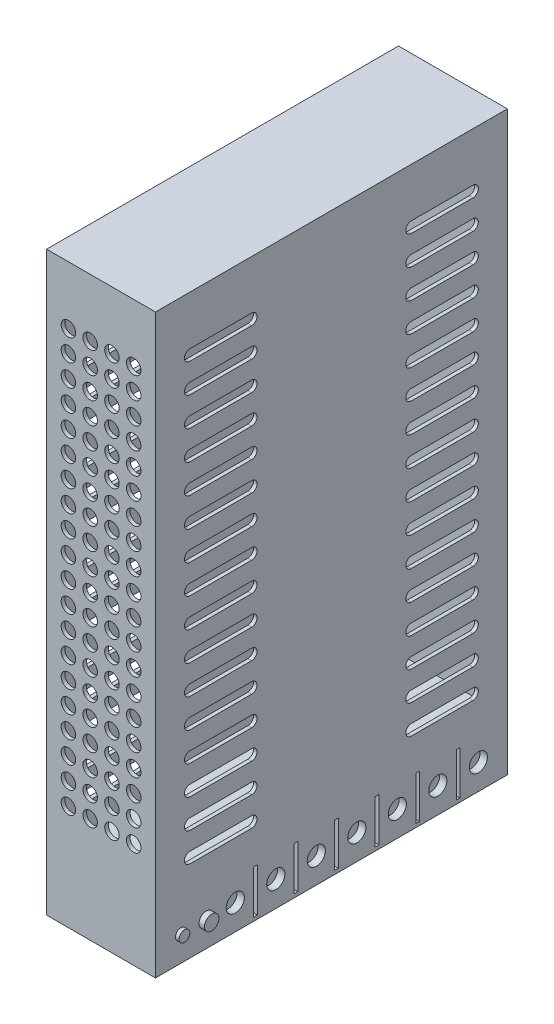
SolidWorks part; units mm, degrees
ref_plane "Front Plane" through (0, 0, 0) normal (0, 0, 1) x (1, 0, 0)
ref_plane "Top Plane" through (0, 0, 0) normal (0, 1, 0) x (1, 0, 0)
ref_plane "Right Plane" through (0, 0, 0) normal (1, 0, 0) x (0, 0, -1)
sketch "Sketch1" plane through (0, 0, 0) normal (0, 0, 1) x (1, 0, 0)
  line L1 (-15, 14) -> (15, 14)
  line L2 (-15, 14) -> (-15, 159)
  line L3 (-15, 159) -> (15, 159)
  line L4 (15, 14) -> (15, 159)
extrude "Case" add sketch "Sketch1" along normal blind 97
shell "Case_shell" thickness 1
sketch "Sketch2" plane through (0, 0, 0) normal (0, 0, 1) x (1, 0, 0)
  line L1 (-15, 0) -> (15, 0)
  line L2 (-15, 0) -> (-15, 14)
  line L3 (-15, 14) -> (15, 14)
  line L4 (15, 0) -> (15, 14)
extrude "Terminal_block" add sketch "Sketch2" along normal blind 97
ref_plane "Plane_x15" through (15, 0, 0) normal (1, 0, 0) x (0, 0, -1)
sketch "Sketch3" plane through (15, 0, 0) normal (1, 0, 0) x (0, 0, -1)
  circle A0 centre (-83, 7) radius 2
extrude "Pot" add sketch "Sketch3" along normal blind 1.5
sketch "Sketch4" plane through (15, 0, 0) normal (1, 0, 0) x (0, 0, -1)
  circle A0 centre (-90, 7) radius 1.5
extrude "LED" add sketch "Sketch4" along normal blind 1
ref_plane "Plane_z97" through (0, 0, 97) normal (0, 0, 1) x (1, 0, 0)
sketch "Sketch5" plane through (0, 0, 97) normal (0, 0, 1) x (1, 0, 0)
  circle A0 centre (-9, 29) radius 2
  circle A1 centre (-9, 35) radius 2
  circle A2 centre (-9, 41) radius 2
  circle A3 centre (-9, 47) radius 2
  circle A4 centre (-9, 53) radius 2
  circle A5 centre (-9, 59) radius 2
  circle A6 centre (-9, 65) radius 2
  circle A7 centre (-9, 71) radius 2
  circle A8 centre (-9, 77) radius 2
  circle A9 centre (-9, 83) radius 2
  circle A10 centre (-9, 89) radius 2
  circle A11 centre (-9, 95) radius 2
  circle A12 centre (-9, 101) radius 2
  circle A13 centre (-9, 107) radius 2
  circle A14 centre (-9, 113) radius 2
  circle A15 centre (-9, 119) radius 2
  circle A16 centre (-9, 125) radius 2
  circle A17 centre (-9, 131) radius 2
  circle A18 centre (-9, 137) radius 2
  circle A19 centre (-9, 143) radius 2
  circle A20 centre (-3, 29) radius 2
  circle A21 centre (-3, 35) radius 2
  circle A22 centre (-3, 41) radius 2
  circle A23 centre (-3, 47) radius 2
  circle A24 centre (-3, 53) radius 2
  circle A25 centre (-3, 59) radius 2
  circle A26 centre (-3, 65) radius 2
  circle A27 centre (-3, 71) radius 2
  circle A28 centre (-3, 77) radius 2
  circle A29 centre (-3, 83) radius 2
  circle A30 centre (-3, 89) radius 2
  circle A31 centre (-3, 95) radius 2
  circle A32 centre (-3, 101) radius 2
  circle A33 centre (-3, 107) radius 2
  circle A34 centre (-3, 113) radius 2
  circle A35 centre (-3, 119) radius 2
  circle A36 centre (-3, 125) radius 2
  circle A37 centre (-3, 131) radius 2
  circle A38 centre (-3, 137) radius 2
  circle A39 centre (-3, 143) radius 2
  circle A40 centre (3, 29) radius 2
  circle A41 centre (3, 35) radius 2
  circle A42 centre (3, 41) radius 2
  circle A43 centre (3, 47) radius 2
  circle A44 centre (3, 53) radius 2
  circle A45 centre (3, 59) radius 2
  circle A46 centre (3, 65) radius 2
  circle A47 centre (3, 71) radius 2
  circle A48 centre (3, 77) radius 2
  circle A49 centre (3, 83) radius 2
  circle A50 centre (3, 89) radius 2
  circle A51 centre (3, 95) radius 2
  circle A52 centre (3, 101) radius 2
  circle A53 centre (3, 107) radius 2
  circle A54 centre (3, 113) radius 2
  circle A55 centre (3, 119) radius 2
  circle A56 centre (3, 125) radius 2
  circle A57 centre (3, 131) radius 2
  circle A58 centre (3, 137) radius 2
  circle A59 centre (3, 143) radius 2
  circle A60 centre (9, 29) radius 2
  circle A61 centre (9, 35) radius 2
  circle A62 centre (9, 41) radius 2
  circle A63 centre (9, 47) radius 2
  circle A64 centre (9, 53) radius 2
  circle A65 centre (9, 59) radius 2
  circle A66 centre (9, 65) radius 2
  circle A67 centre (9, 71) radius 2
  circle A68 centre (9, 77) radius 2
  circle A69 centre (9, 83) radius 2
  circle A70 centre (9, 89) radius 2
  circle A71 centre (9, 95) radius 2
  circle A72 centre (9, 101) radius 2
  circle A73 centre (9, 107) radius 2
  circle A74 centre (9, 113) radius 2
  circle A75 centre (9, 119) radius 2
  circle A76 centre (9, 125) radius 2
  circle A77 centre (9, 131) radius 2
  circle A78 centre (9, 137) radius 2
  circle A79 centre (9, 143) radius 2
extrude "Perforation" cut sketch "Sketch5" against normal blind 1
sketch "Sketch6" plane through (15, 0, 0) normal (1, 0, 0) x (0, 0, -1)
  line L0 (-9.5, 24) -> (-26.5, 24) construction
  line L1 (-9.5, 22.5) -> (-26.5, 22.5)
  line L2 (-9.5, 25.5) -> (-26.5, 25.5)
  line L3 (-70.5, 24) -> (-87.5, 24) construction
  line L4 (-70.5, 22.5) -> (-87.5, 22.5)
  line L5 (-70.5, 25.5) -> (-87.5, 25.5)
  line L6 (-9.5, 32) -> (-26.5, 32) construction
  line L7 (-9.5, 30.5) -> (-26.5, 30.5)
  line L8 (-9.5, 33.5) -> (-26.5, 33.5)
  line L9 (-70.5, 32) -> (-87.5, 32) construction
  line L10 (-70.5, 30.5) -> (-87.5, 30.5)
  line L11 (-70.5, 33.5) -> (-87.5, 33.5)
  line L12 (-9.5, 40) -> (-26.5, 40) construction
  line L13 (-9.5, 38.5) -> (-26.5, 38.5)
  line L14 (-9.5, 41.5) -> (-26.5, 41.5)
  line L15 (-70.5, 40) -> (-87.5, 40) construction
  line L16 (-70.5, 38.5) -> (-87.5, 38.5)
  line L17 (-70.5, 41.5) -> (-87.5, 41.5)
  line L18 (-9.5, 48) -> (-26.5, 48) construction
  line L19 (-9.5, 46.5) -> (-26.5, 46.5)
  line L20 (-9.5, 49.5) -> (-26.5, 49.5)
  line L21 (-70.5, 48) -> (-87.5, 48) construction
  line L22 (-70.5, 46.5) -> (-87.5, 46.5)
  line L23 (-70.5, 49.5) -> (-87.5, 49.5)
  line L24 (-9.5, 56) -> (-26.5, 56) construction
  line L25 (-9.5, 54.5) -> (-26.5, 54.5)
  line L26 (-9.5, 57.5) -> (-26.5, 57.5)
  line L27 (-70.5, 56) -> (-87.5, 56) construction
  line L28 (-70.5, 54.5) -> (-87.5, 54.5)
  line L29 (-70.5, 57.5) -> (-87.5, 57.5)
  line L30 (-9.5, 64) -> (-26.5, 64) construction
  line L31 (-9.5, 62.5) -> (-26.5, 62.5)
  line L32 (-9.5, 65.5) -> (-26.5, 65.5)
  line L33 (-70.5, 64) -> (-87.5, 64) construction
  line L34 (-70.5, 62.5) -> (-87.5, 62.5)
  line L35 (-70.5, 65.5) -> (-87.5, 65.5)
  line L36 (-9.5, 72) -> (-26.5, 72) construction
  line L37 (-9.5, 70.5) -> (-26.5, 70.5)
  line L38 (-9.5, 73.5) -> (-26.5, 73.5)
  line L39 (-70.5, 72) -> (-87.5, 72) construction
  line L40 (-70.5, 70.5) -> (-87.5, 70.5)
  line L41 (-70.5, 73.5) -> (-87.5, 73.5)
  line L42 (-9.5, 80) -> (-26.5, 80) construction
  line L43 (-9.5, 78.5) -> (-26.5, 78.5)
  line L44 (-9.5, 81.5) -> (-26.5, 81.5)
  line L45 (-70.5, 80) -> (-87.5, 80) construction
  line L46 (-70.5, 78.5) -> (-87.5, 78.5)
  line L47 (-70.5, 81.5) -> (-87.5, 81.5)
  line L48 (-9.5, 88) -> (-26.5, 88) construction
  line L49 (-9.5, 86.5) -> (-26.5, 86.5)
  line L50 (-9.5, 89.5) -> (-26.5, 89.5)
  line L51 (-70.5, 88) -> (-87.5, 88) construction
  line L52 (-70.5, 86.5) -> (-87.5, 86.5)
  line L53 (-70.5, 89.5) -> (-87.5, 89.5)
  line L54 (-9.5, 96) -> (-26.5, 96) construction
  line L55 (-9.5, 94.5) -> (-26.5, 94.5)
  line L56 (-9.5, 97.5) -> (-26.5, 97.5)
  line L57 (-70.5, 96) -> (-87.5, 96) construction
  line L58 (-70.5, 94.5) -> (-87.5, 94.5)
  line L59 (-70.5, 97.5) -> (-87.5, 97.5)
  line L60 (-9.5, 104) -> (-26.5, 104) construction
  line L61 (-9.5, 102.5) -> (-26.5, 102.5)
  line L62 (-9.5, 105.5) -> (-26.5, 105.5)
  line L63 (-70.5, 104) -> (-87.5, 104) construction
  line L64 (-70.5, 102.5) -> (-87.5, 102.5)
  line L65 (-70.5, 105.5) -> (-87.5, 105.5)
  line L66 (-9.5, 112) -> (-26.5, 112) construction
  line L67 (-9.5, 110.5) -> (-26.5, 110.5)
  line L68 (-9.5, 113.5) -> (-26.5, 113.5)
  line L69 (-70.5, 112) -> (-87.5, 112) construction
  line L70 (-70.5, 110.5) -> (-87.5, 110.5)
  line L71 (-70.5, 113.5) -> (-87.5, 113.5)
  line L72 (-9.5, 120) -> (-26.5, 120) construction
  line L73 (-9.5, 118.5) -> (-26.5, 118.5)
  line L74 (-9.5, 121.5) -> (-26.5, 121.5)
  line L75 (-70.5, 120) -> (-87.5, 120) construction
  line L76 (-70.5, 118.5) -> (-87.5, 118.5)
  line L77 (-70.5, 121.5) -> (-87.5, 121.5)
  line L78 (-9.5, 128) -> (-26.5, 128) construction
  line L79 (-9.5, 126.5) -> (-26.5, 126.5)
  line L80 (-9.5, 129.5) -> (-26.5, 129.5)
  line L81 (-70.5, 128) -> (-87.5, 128) construction
  line L82 (-70.5, 126.5) -> (-87.5, 126.5)
  line L83 (-70.5, 129.5) -> (-87.5, 129.5)
  line L84 (-9.5, 136) -> (-26.5, 136) construction
  line L85 (-9.5, 134.5) -> (-26.5, 134.5)
  line L86 (-9.5, 137.5) -> (-26.5, 137.5)
  line L87 (-70.5, 136) -> (-87.5, 136) construction
  line L88 (-70.5, 134.5) -> (-87.5, 134.5)
  line L89 (-70.5, 137.5) -> (-87.5, 137.5)
  line L90 (-9.5, 144) -> (-26.5, 144) construction
  line L91 (-9.5, 142.5) -> (-26.5, 142.5)
  line L92 (-9.5, 145.5) -> (-26.5, 145.5)
  line L93 (-70.5, 144) -> (-87.5, 144) construction
  line L94 (-70.5, 142.5) -> (-87.5, 142.5)
  line L95 (-70.5, 145.5) -> (-87.5, 145.5)
  arc A0 (-9.5, 22.5) -> (-9.5, 25.5) centre (-9.5, 24) ccw
  arc A1 (-26.5, 25.5) -> (-26.5, 22.5) centre (-26.5, 24) ccw
  arc A2 (-70.5, 22.5) -> (-70.5, 25.5) centre (-70.5, 24) ccw
  arc A3 (-87.5, 25.5) -> (-87.5, 22.5) centre (-87.5, 24) ccw
  arc A4 (-9.5, 30.5) -> (-9.5, 33.5) centre (-9.5, 32) ccw
  arc A5 (-26.5, 33.5) -> (-26.5, 30.5) centre (-26.5, 32) ccw
  arc A6 (-70.5, 30.5) -> (-70.5, 33.5) centre (-70.5, 32) ccw
  arc A7 (-87.5, 33.5) -> (-87.5, 30.5) centre (-87.5, 32) ccw
  arc A8 (-9.5, 38.5) -> (-9.5, 41.5) centre (-9.5, 40) ccw
  arc A9 (-26.5, 41.5) -> (-26.5, 38.5) centre (-26.5, 40) ccw
  arc A10 (-70.5, 38.5) -> (-70.5, 41.5) centre (-70.5, 40) ccw
  arc A11 (-87.5, 41.5) -> (-87.5, 38.5) centre (-87.5, 40) ccw
  arc A12 (-9.5, 46.5) -> (-9.5, 49.5) centre (-9.5, 48) ccw
  arc A13 (-26.5, 49.5) -> (-26.5, 46.5) centre (-26.5, 48) ccw
  arc A14 (-70.5, 46.5) -> (-70.5, 49.5) centre (-70.5, 48) ccw
  arc A15 (-87.5, 49.5) -> (-87.5, 46.5) centre (-87.5, 48) ccw
  arc A16 (-9.5, 54.5) -> (-9.5, 57.5) centre (-9.5, 56) ccw
  arc A17 (-26.5, 57.5) -> (-26.5, 54.5) centre (-26.5, 56) ccw
  arc A18 (-70.5, 54.5) -> (-70.5, 57.5) centre (-70.5, 56) ccw
  arc A19 (-87.5, 57.5) -> (-87.5, 54.5) centre (-87.5, 56) ccw
  arc A20 (-9.5, 62.5) -> (-9.5, 65.5) centre (-9.5, 64) ccw
  arc A21 (-26.5, 65.5) -> (-26.5, 62.5) centre (-26.5, 64) ccw
  arc A22 (-70.5, 62.5) -> (-70.5, 65.5) centre (-70.5, 64) ccw
  arc A23 (-87.5, 65.5) -> (-87.5, 62.5) centre (-87.5, 64) ccw
  arc A24 (-9.5, 70.5) -> (-9.5, 73.5) centre (-9.5, 72) ccw
  arc A25 (-26.5, 73.5) -> (-26.5, 70.5) centre (-26.5, 72) ccw
  arc A26 (-70.5, 70.5) -> (-70.5, 73.5) centre (-70.5, 72) ccw
  arc A27 (-87.5, 73.5) -> (-87.5, 70.5) centre (-87.5, 72) ccw
  arc A28 (-9.5, 78.5) -> (-9.5, 81.5) centre (-9.5, 80) ccw
  arc A29 (-26.5, 81.5) -> (-26.5, 78.5) centre (-26.5, 80) ccw
  arc A30 (-70.5, 78.5) -> (-70.5, 81.5) centre (-70.5, 80) ccw
  arc A31 (-87.5, 81.5) -> (-87.5, 78.5) centre (-87.5, 80) ccw
  arc A32 (-9.5, 86.5) -> (-9.5, 89.5) centre (-9.5, 88) ccw
  arc A33 (-26.5, 89.5) -> (-26.5, 86.5) centre (-26.5, 88) ccw
  arc A34 (-70.5, 86.5) -> (-70.5, 89.5) centre (-70.5, 88) ccw
  arc A35 (-87.5, 89.5) -> (-87.5, 86.5) centre (-87.5, 88) ccw
  arc A36 (-9.5, 94.5) -> (-9.5, 97.5) centre (-9.5, 96) ccw
  arc A37 (-26.5, 97.5) -> (-26.5, 94.5) centre (-26.5, 96) ccw
  arc A38 (-70.5, 94.5) -> (-70.5, 97.5) centre (-70.5, 96) ccw
  arc A39 (-87.5, 97.5) -> (-87.5, 94.5) centre (-87.5, 96) ccw
  arc A40 (-9.5, 102.5) -> (-9.5, 105.5) centre (-9.5, 104) ccw
  arc A41 (-26.5, 105.5) -> (-26.5, 102.5) centre (-26.5, 104) ccw
  arc A42 (-70.5, 102.5) -> (-70.5, 105.5) centre (-70.5, 104) ccw
  arc A43 (-87.5, 105.5) -> (-87.5, 102.5) centre (-87.5, 104) ccw
  arc A44 (-9.5, 110.5) -> (-9.5, 113.5) centre (-9.5, 112) ccw
  arc A45 (-26.5, 113.5) -> (-26.5, 110.5) centre (-26.5, 112) ccw
  arc A46 (-70.5, 110.5) -> (-70.5, 113.5) centre (-70.5, 112) ccw
  arc A47 (-87.5, 113.5) -> (-87.5, 110.5) centre (-87.5, 112) ccw
  arc A48 (-9.5, 118.5) -> (-9.5, 121.5) centre (-9.5, 120) ccw
  arc A49 (-26.5, 121.5) -> (-26.5, 118.5) centre (-26.5, 120) ccw
  arc A50 (-70.5, 118.5) -> (-70.5, 121.5) centre (-70.5, 120) ccw
  arc A51 (-87.5, 121.5) -> (-87.5, 118.5) centre (-87.5, 120) ccw
  arc A52 (-9.5, 126.5) -> (-9.5, 129.5) centre (-9.5, 128) ccw
  arc A53 (-26.5, 129.5) -> (-26.5, 126.5) centre (-26.5, 128) ccw
  arc A54 (-70.5, 126.5) -> (-70.5, 129.5) centre (-70.5, 128) ccw
  arc A55 (-87.5, 129.5) -> (-87.5, 126.5) centre (-87.5, 128) ccw
  arc A56 (-9.5, 134.5) -> (-9.5, 137.5) centre (-9.5, 136) ccw
  arc A57 (-26.5, 137.5) -> (-26.5, 134.5) centre (-26.5, 136) ccw
  arc A58 (-70.5, 134.5) -> (-70.5, 137.5) centre (-70.5, 136) ccw
  arc A59 (-87.5, 137.5) -> (-87.5, 134.5) centre (-87.5, 136) ccw
  arc A60 (-9.5, 142.5) -> (-9.5, 145.5) centre (-9.5, 144) ccw
  arc A61 (-26.5, 145.5) -> (-26.5, 142.5) centre (-26.5, 144) ccw
  arc A62 (-70.5, 142.5) -> (-70.5, 145.5) centre (-70.5, 144) ccw
  arc A63 (-87.5, 145.5) -> (-87.5, 142.5) centre (-87.5, 144) ccw
  point P2 (-18, 24)
  point P7 (-79, 24)
  point P14 (-18, 32)
  point P21 (-79, 32)
  point P28 (-18, 40)
  point P35 (-79, 40)
  point P42 (-18, 48)
  point P49 (-79, 48)
  point P56 (-18, 56)
  point P63 (-79, 56)
  point P70 (-18, 64)
  point P77 (-79, 64)
  point P84 (-18, 72)
  point P91 (-79, 72)
  point P98 (-18, 80)
  point P105 (-79, 80)
  point P112 (-18, 88)
  point P119 (-79, 88)
  point P126 (-18, 96)
  point P133 (-79, 96)
  point P140 (-18, 104)
  point P147 (-79, 104)
  point P154 (-18, 112)
  point P161 (-79, 112)
  point P168 (-18, 120)
  point P175 (-79, 120)
  point P182 (-18, 128)
  point P189 (-79, 128)
  point P196 (-18, 136)
  point P203 (-79, 136)
  point P210 (-18, 144)
  point P217 (-79, 144)
  point P224 (0, 0)
extrude "Vents_R" cut sketch "Sketch6" against normal blind 1
ref_plane "Plane_xm15" through (-15, 0, 0) normal (1, 0, 0) x (0, 0, -1)
sketch "Sketch7" plane through (-15, 0, 0) normal (1, 0, 0) x (0, 0, -1)
  line L0 (-9.5, 24) -> (-26.5, 24) construction
  line L1 (-9.5, 22.5) -> (-26.5, 22.5)
  line L2 (-9.5, 25.5) -> (-26.5, 25.5)
  line L3 (-70.5, 24) -> (-87.5, 24) construction
  line L4 (-70.5, 22.5) -> (-87.5, 22.5)
  line L5 (-70.5, 25.5) -> (-87.5, 25.5)
  line L6 (-9.5, 32) -> (-26.5, 32) construction
  line L7 (-9.5, 30.5) -> (-26.5, 30.5)
  line L8 (-9.5, 33.5) -> (-26.5, 33.5)
  line L9 (-70.5, 32) -> (-87.5, 32) construction
  line L10 (-70.5, 30.5) -> (-87.5, 30.5)
  line L11 (-70.5, 33.5) -> (-87.5, 33.5)
  line L12 (-9.5, 40) -> (-26.5, 40) construction
  line L13 (-9.5, 38.5) -> (-26.5, 38.5)
  line L14 (-9.5, 41.5) -> (-26.5, 41.5)
  line L15 (-70.5, 40) -> (-87.5, 40) construction
  line L16 (-70.5, 38.5) -> (-87.5, 38.5)
  line L17 (-70.5, 41.5) -> (-87.5, 41.5)
  line L18 (-9.5, 48) -> (-26.5, 48) construction
  line L19 (-9.5, 46.5) -> (-26.5, 46.5)
  line L20 (-9.5, 49.5) -> (-26.5, 49.5)
  line L21 (-70.5, 48) -> (-87.5, 48) construction
  line L22 (-70.5, 46.5) -> (-87.5, 46.5)
  line L23 (-70.5, 49.5) -> (-87.5, 49.5)
  line L24 (-9.5, 56) -> (-26.5, 56) construction
  line L25 (-9.5, 54.5) -> (-26.5, 54.5)
  line L26 (-9.5, 57.5) -> (-26.5, 57.5)
  line L27 (-70.5, 56) -> (-87.5, 56) construction
  line L28 (-70.5, 54.5) -> (-87.5, 54.5)
  line L29 (-70.5, 57.5) -> (-87.5, 57.5)
  line L30 (-9.5, 64) -> (-26.5, 64) construction
  line L31 (-9.5, 62.5) -> (-26.5, 62.5)
  line L32 (-9.5, 65.5) -> (-26.5, 65.5)
  line L33 (-70.5, 64) -> (-87.5, 64) construction
  line L34 (-70.5, 62.5) -> (-87.5, 62.5)
  line L35 (-70.5, 65.5) -> (-87.5, 65.5)
  line L36 (-9.5, 72) -> (-26.5, 72) construction
  line L37 (-9.5, 70.5) -> (-26.5, 70.5)
  line L38 (-9.5, 73.5) -> (-26.5, 73.5)
  line L39 (-70.5, 72) -> (-87.5, 72) construction
  line L40 (-70.5, 70.5) -> (-87.5, 70.5)
  line L41 (-70.5, 73.5) -> (-87.5, 73.5)
  line L42 (-9.5, 80) -> (-26.5, 80) construction
  line L43 (-9.5, 78.5) -> (-26.5, 78.5)
  line L44 (-9.5, 81.5) -> (-26.5, 81.5)
  line L45 (-70.5, 80) -> (-87.5, 80) construction
  line L46 (-70.5, 78.5) -> (-87.5, 78.5)
  line L47 (-70.5, 81.5) -> (-87.5, 81.5)
  line L48 (-9.5, 88) -> (-26.5, 88) construction
  line L49 (-9.5, 86.5) -> (-26.5, 86.5)
  line L50 (-9.5, 89.5) -> (-26.5, 89.5)
  line L51 (-70.5, 88) -> (-87.5, 88) construction
  line L52 (-70.5, 86.5) -> (-87.5, 86.5)
  line L53 (-70.5, 89.5) -> (-87.5, 89.5)
  line L54 (-9.5, 96) -> (-26.5, 96) construction
  line L55 (-9.5, 94.5) -> (-26.5, 94.5)
  line L56 (-9.5, 97.5) -> (-26.5, 97.5)
  line L57 (-70.5, 96) -> (-87.5, 96) construction
  line L58 (-70.5, 94.5) -> (-87.5, 94.5)
  line L59 (-70.5, 97.5) -> (-87.5, 97.5)
  line L60 (-9.5, 104) -> (-26.5, 104) construction
  line L61 (-9.5, 102.5) -> (-26.5, 102.5)
  line L62 (-9.5, 105.5) -> (-26.5, 105.5)
  line L63 (-70.5, 104) -> (-87.5, 104) construction
  line L64 (-70.5, 102.5) -> (-87.5, 102.5)
  line L65 (-70.5, 105.5) -> (-87.5, 105.5)
  line L66 (-9.5, 112) -> (-26.5, 112) construction
  line L67 (-9.5, 110.5) -> (-26.5, 110.5)
  line L68 (-9.5, 113.5) -> (-26.5, 113.5)
  line L69 (-70.5, 112) -> (-87.5, 112) construction
  line L70 (-70.5, 110.5) -> (-87.5, 110.5)
  line L71 (-70.5, 113.5) -> (-87.5, 113.5)
  line L72 (-9.5, 120) -> (-26.5, 120) construction
  line L73 (-9.5, 118.5) -> (-26.5, 118.5)
  line L74 (-9.5, 121.5) -> (-26.5, 121.5)
  line L75 (-70.5, 120) -> (-87.5, 120) construction
  line L76 (-70.5, 118.5) -> (-87.5, 118.5)
  line L77 (-70.5, 121.5) -> (-87.5, 121.5)
  line L78 (-9.5, 128) -> (-26.5, 128) construction
  line L79 (-9.5, 126.5) -> (-26.5, 126.5)
  line L80 (-9.5, 129.5) -> (-26.5, 129.5)
  line L81 (-70.5, 128) -> (-87.5, 128) construction
  line L82 (-70.5, 126.5) -> (-87.5, 126.5)
  line L83 (-70.5, 129.5) -> (-87.5, 129.5)
  line L84 (-9.5, 136) -> (-26.5, 136) construction
  line L85 (-9.5, 134.5) -> (-26.5, 134.5)
  line L86 (-9.5, 137.5) -> (-26.5, 137.5)
  line L87 (-70.5, 136) -> (-87.5, 136) construction
  line L88 (-70.5, 134.5) -> (-87.5, 134.5)
  line L89 (-70.5, 137.5) -> (-87.5, 137.5)
  line L90 (-9.5, 144) -> (-26.5, 144) construction
  line L91 (-9.5, 142.5) -> (-26.5, 142.5)
  line L92 (-9.5, 145.5) -> (-26.5, 145.5)
  line L93 (-70.5, 144) -> (-87.5, 144) construction
  line L94 (-70.5, 142.5) -> (-87.5, 142.5)
  line L95 (-70.5, 145.5) -> (-87.5, 145.5)
  arc A0 (-9.5, 22.5) -> (-9.5, 25.5) centre (-9.5, 24) ccw
  arc A1 (-26.5, 25.5) -> (-26.5, 22.5) centre (-26.5, 24) ccw
  arc A2 (-70.5, 22.5) -> (-70.5, 25.5) centre (-70.5, 24) ccw
  arc A3 (-87.5, 25.5) -> (-87.5, 22.5) centre (-87.5, 24) ccw
  arc A4 (-9.5, 30.5) -> (-9.5, 33.5) centre (-9.5, 32) ccw
  arc A5 (-26.5, 33.5) -> (-26.5, 30.5) centre (-26.5, 32) ccw
  arc A6 (-70.5, 30.5) -> (-70.5, 33.5) centre (-70.5, 32) ccw
  arc A7 (-87.5, 33.5) -> (-87.5, 30.5) centre (-87.5, 32) ccw
  arc A8 (-9.5, 38.5) -> (-9.5, 41.5) centre (-9.5, 40) ccw
  arc A9 (-26.5, 41.5) -> (-26.5, 38.5) centre (-26.5, 40) ccw
  arc A10 (-70.5, 38.5) -> (-70.5, 41.5) centre (-70.5, 40) ccw
  arc A11 (-87.5, 41.5) -> (-87.5, 38.5) centre (-87.5, 40) ccw
  arc A12 (-9.5, 46.5) -> (-9.5, 49.5) centre (-9.5, 48) ccw
  arc A13 (-26.5, 49.5) -> (-26.5, 46.5) centre (-26.5, 48) ccw
  arc A14 (-70.5, 46.5) -> (-70.5, 49.5) centre (-70.5, 48) ccw
  arc A15 (-87.5, 49.5) -> (-87.5, 46.5) centre (-87.5, 48) ccw
  arc A16 (-9.5, 54.5) -> (-9.5, 57.5) centre (-9.5, 56) ccw
  arc A17 (-26.5, 57.5) -> (-26.5, 54.5) centre (-26.5, 56) ccw
  arc A18 (-70.5, 54.5) -> (-70.5, 57.5) centre (-70.5, 56) ccw
  arc A19 (-87.5, 57.5) -> (-87.5, 54.5) centre (-87.5, 56) ccw
  arc A20 (-9.5, 62.5) -> (-9.5, 65.5) centre (-9.5, 64) ccw
  arc A21 (-26.5, 65.5) -> (-26.5, 62.5) centre (-26.5, 64) ccw
  arc A22 (-70.5, 62.5) -> (-70.5, 65.5) centre (-70.5, 64) ccw
  arc A23 (-87.5, 65.5) -> (-87.5, 62.5) centre (-87.5, 64) ccw
  arc A24 (-9.5, 70.5) -> (-9.5, 73.5) centre (-9.5, 72) ccw
  arc A25 (-26.5, 73.5) -> (-26.5, 70.5) centre (-26.5, 72) ccw
  arc A26 (-70.5, 70.5) -> (-70.5, 73.5) centre (-70.5, 72) ccw
  arc A27 (-87.5, 73.5) -> (-87.5, 70.5) centre (-87.5, 72) ccw
  arc A28 (-9.5, 78.5) -> (-9.5, 81.5) centre (-9.5, 80) ccw
  arc A29 (-26.5, 81.5) -> (-26.5, 78.5) centre (-26.5, 80) ccw
  arc A30 (-70.5, 78.5) -> (-70.5, 81.5) centre (-70.5, 80) ccw
  arc A31 (-87.5, 81.5) -> (-87.5, 78.5) centre (-87.5, 80) ccw
  arc A32 (-9.5, 86.5) -> (-9.5, 89.5) centre (-9.5, 88) ccw
  arc A33 (-26.5, 89.5) -> (-26.5, 86.5) centre (-26.5, 88) ccw
  arc A34 (-70.5, 86.5) -> (-70.5, 89.5) centre (-70.5, 88) ccw
  arc A35 (-87.5, 89.5) -> (-87.5, 86.5) centre (-87.5, 88) ccw
  arc A36 (-9.5, 94.5) -> (-9.5, 97.5) centre (-9.5, 96) ccw
  arc A37 (-26.5, 97.5) -> (-26.5, 94.5) centre (-26.5, 96) ccw
  arc A38 (-70.5, 94.5) -> (-70.5, 97.5) centre (-70.5, 96) ccw
  arc A39 (-87.5, 97.5) -> (-87.5, 94.5) centre (-87.5, 96) ccw
  arc A40 (-9.5, 102.5) -> (-9.5, 105.5) centre (-9.5, 104) ccw
  arc A41 (-26.5, 105.5) -> (-26.5, 102.5) centre (-26.5, 104) ccw
  arc A42 (-70.5, 102.5) -> (-70.5, 105.5) centre (-70.5, 104) ccw
  arc A43 (-87.5, 105.5) -> (-87.5, 102.5) centre (-87.5, 104) ccw
  arc A44 (-9.5, 110.5) -> (-9.5, 113.5) centre (-9.5, 112) ccw
  arc A45 (-26.5, 113.5) -> (-26.5, 110.5) centre (-26.5, 112) ccw
  arc A46 (-70.5, 110.5) -> (-70.5, 113.5) centre (-70.5, 112) ccw
  arc A47 (-87.5, 113.5) -> (-87.5, 110.5) centre (-87.5, 112) ccw
  arc A48 (-9.5, 118.5) -> (-9.5, 121.5) centre (-9.5, 120) ccw
  arc A49 (-26.5, 121.5) -> (-26.5, 118.5) centre (-26.5, 120) ccw
  arc A50 (-70.5, 118.5) -> (-70.5, 121.5) centre (-70.5, 120) ccw
  arc A51 (-87.5, 121.5) -> (-87.5, 118.5) centre (-87.5, 120) ccw
  arc A52 (-9.5, 126.5) -> (-9.5, 129.5) centre (-9.5, 128) ccw
  arc A53 (-26.5, 129.5) -> (-26.5, 126.5) centre (-26.5, 128) ccw
  arc A54 (-70.5, 126.5) -> (-70.5, 129.5) centre (-70.5, 128) ccw
  arc A55 (-87.5, 129.5) -> (-87.5, 126.5) centre (-87.5, 128) ccw
  arc A56 (-9.5, 134.5) -> (-9.5, 137.5) centre (-9.5, 136) ccw
  arc A57 (-26.5, 137.5) -> (-26.5, 134.5) centre (-26.5, 136) ccw
  arc A58 (-70.5, 134.5) -> (-70.5, 137.5) centre (-70.5, 136) ccw
  arc A59 (-87.5, 137.5) -> (-87.5, 134.5) centre (-87.5, 136) ccw
  arc A60 (-9.5, 142.5) -> (-9.5, 145.5) centre (-9.5, 144) ccw
  arc A61 (-26.5, 145.5) -> (-26.5, 142.5) centre (-26.5, 144) ccw
  arc A62 (-70.5, 142.5) -> (-70.5, 145.5) centre (-70.5, 144) ccw
  arc A63 (-87.5, 145.5) -> (-87.5, 142.5) centre (-87.5, 144) ccw
  point P2 (-18, 24)
  point P7 (-79, 24)
  point P14 (-18, 32)
  point P21 (-79, 32)
  point P28 (-18, 40)
  point P35 (-79, 40)
  point P42 (-18, 48)
  point P49 (-79, 48)
  point P56 (-18, 56)
  point P63 (-79, 56)
  point P70 (-18, 64)
  point P77 (-79, 64)
  point P84 (-18, 72)
  point P91 (-79, 72)
  point P98 (-18, 80)
  point P105 (-79, 80)
  point P112 (-18, 88)
  point P119 (-79, 88)
  point P126 (-18, 96)
  point P133 (-79, 96)
  point P140 (-18, 104)
  point P147 (-79, 104)
  point P154 (-18, 112)
  point P161 (-79, 112)
  point P168 (-18, 120)
  point P175 (-79, 120)
  point P182 (-18, 128)
  point P189 (-79, 128)
  point P196 (-18, 136)
  point P203 (-79, 136)
  point P210 (-18, 144)
  point P217 (-79, 144)
  point P224 (0, 0)
extrude "Vents_L" cut sketch "Sketch7" along normal blind 1
sketch "Sketch8" plane through (15, 0, 0) normal (1, 0, 0) x (0, 0, -1)
  circle A0 centre (-8, 7) radius 2.5
  circle A1 centre (-19.1667, 7) radius 2.5
  circle A2 centre (-30.3333, 7) radius 2.5
  circle A3 centre (-41.5, 7) radius 2.5
  circle A4 centre (-52.6667, 7) radius 2.5
  circle A5 centre (-63.8333, 7) radius 2.5
  circle A6 centre (-75, 7) radius 2.5
extrude "Screws" cut sketch "Sketch8" against normal blind 2
sketch "Sketch9" plane through (15, 0, 0) normal (1, 0, 0) x (0, 0, -1)
  line L1 (-13.0833, 1) -> (-14.0833, 1)
  line L2 (-13.0833, 1) -> (-13.0833, 13)
  line L3 (-13.0833, 13) -> (-14.0833, 13)
  line L4 (-14.0833, 1) -> (-14.0833, 13)
  line L6 (-24.25, 1) -> (-25.25, 1)
  line L7 (-24.25, 1) -> (-24.25, 13)
  line L8 (-24.25, 13) -> (-25.25, 13)
  line L9 (-25.25, 1) -> (-25.25, 13)
  line L11 (-35.4167, 1) -> (-36.4167, 1)
  line L12 (-35.4167, 1) -> (-35.4167, 13)
  line L13 (-35.4167, 13) -> (-36.4167, 13)
  line L14 (-36.4167, 1) -> (-36.4167, 13)
  line L16 (-46.5833, 1) -> (-47.5833, 1)
  line L17 (-46.5833, 1) -> (-46.5833, 13)
  line L18 (-46.5833, 13) -> (-47.5833, 13)
  line L19 (-47.5833, 1) -> (-47.5833, 13)
  line L21 (-57.75, 1) -> (-58.75, 1)
  line L22 (-57.75, 1) -> (-57.75, 13)
  line L23 (-57.75, 13) -> (-58.75, 13)
  line L24 (-58.75, 1) -> (-58.75, 13)
  line L26 (-68.9167, 1) -> (-69.9167, 1)
  line L27 (-68.9167, 1) -> (-68.9167, 13)
  line L28 (-68.9167, 13) -> (-69.9167, 13)
  line L29 (-69.9167, 1) -> (-69.9167, 13)
extrude "Barriers" cut sketch "Sketch9" against normal blind 3
